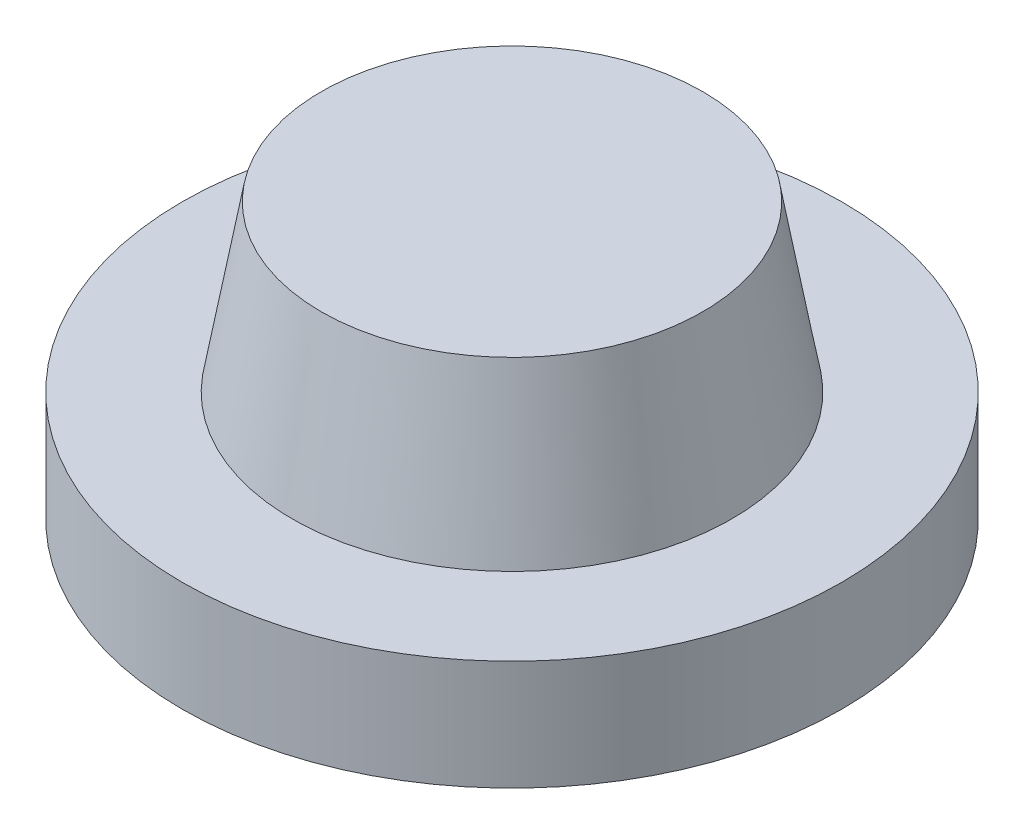
SolidWorks part; units mm, degrees
ref_plane "Front Plane" through (0, 0, 0) normal (0, 0, 1) x (1, 0, 0)
ref_plane "Top Plane" through (0, 0, 0) normal (0, 1, 0) x (1, 0, 0)
ref_plane "Right Plane" through (0, 0, 0) normal (1, 0, 0) x (0, 0, -1)
sketch "Sketch1" plane through (0, 0, 0) normal (0, 0, 1) x (1, 0, 0)
  line L0 (0, 0) -> (0, 47.9899) construction
  line L1 (0, 1.2756) -> (1.7556, 1.2756)
  line L2 (1.7556, 1.2756) -> (1.7556, 0)
  line L3 (1.7556, 0) -> (6, 0)
  line L4 (6, 0) -> (6, 2)
  line L5 (6, 2) -> (4, 2)
  line L6 (4, 2) -> (3.471, 5)
  line L7 (3.471, 5) -> (0, 5)
  line L8 (0, 5) -> (0, 1.2756)
  point P5 (5.1018, 7.8721)
  point P12 (1.7556, 1.2756)
  dimension "D1" = 10
  dimension "D2" = 6
  dimension "D3" = 2
  dimension "D4" = 5
  dimension "D5" = 4
revolve "Revolve1" add sketch "Sketch1" angle 360 about L0
